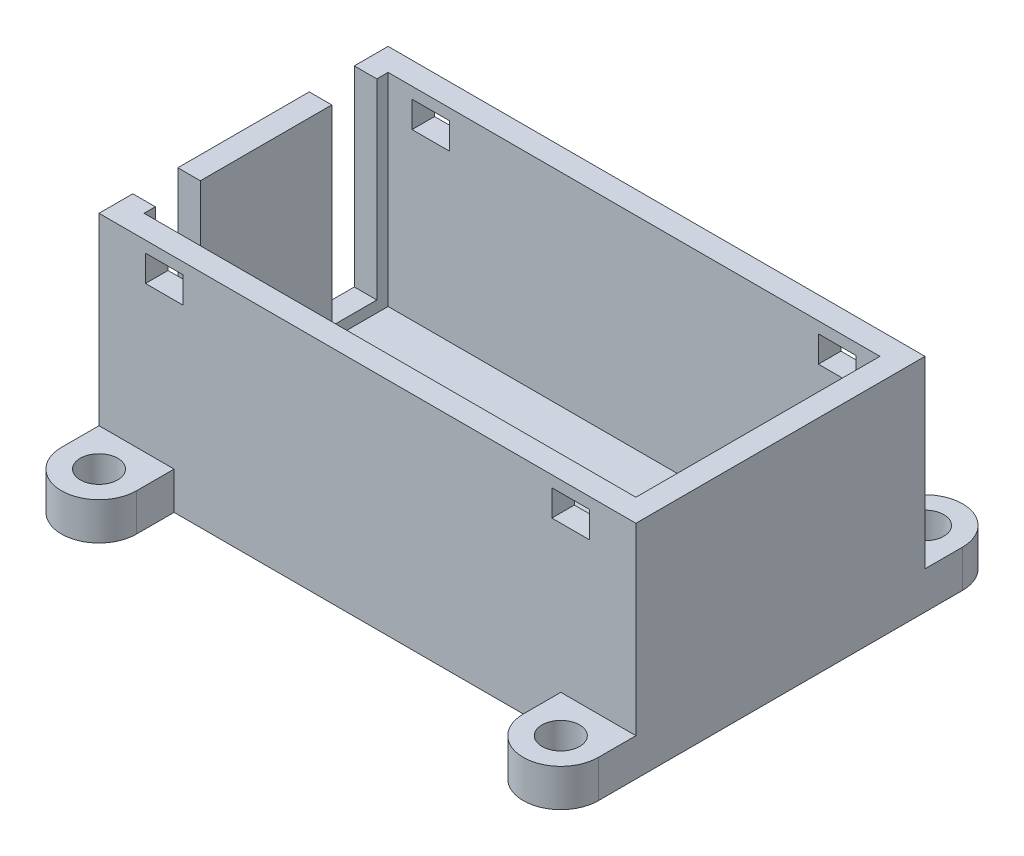
SolidWorks part; units mm, degrees
ref_plane "Front Plane" through (0, 0, 0) normal (0, 0, 1) x (1, 0, 0)
ref_plane "Top Plane" through (0, 0, 0) normal (0, 1, 0) x (1, 0, 0)
ref_plane "Right Plane" through (0, 0, 0) normal (1, 0, 0) x (0, 0, -1)
sketch "Sketch1" plane through (0, 0, 0) normal (0, 1, 0) x (1, 0, 0)
  line L0 (0, 0) -> (3, 0)
  line L1 (0, 0) -> (71.5, 0)
  line L2 (0, 0) -> (0, 38.5)
  line L3 (0, 38.5) -> (71.5, 38.5)
  line L4 (71.5, 0) -> (71.5, 38.5)
  line L5 (3, 0) -> (3, 3)
  line L7 (3, 3) -> (68.5, 3)
  line L8 (3, 3) -> (3, 35.5)
  line L9 (3, 35.5) -> (68.5, 35.5)
  line L10 (68.5, 3) -> (68.5, 35.5)
  dimension "D1" = 71.5
  dimension "D2" = 38.5
  dimension "D3" = 3
  dimension "D4" = 3
  dimension "D5" = 65.5
  dimension "D6" = 32.5
extrude "Boss-Extrude1" add sketch "Sketch1" against normal blind 29.5 contours L2 L3 L4 L1
extrude "Cut-Extrude1" cut sketch "Sketch1<4>" against normal blind 27 contours L8 L9 L10 L7
sketch "Sketch1<4>" plane through (0, 0, 0) normal (0, 1, 0) x (1, 0, 0) same geometry as "Sketch1"
sketch "Sketch3" plane through (0, 0, 0) normal (-1, 0, 0) x (0, 0, 1)
  line L0 (-4.5, -25.5) -> (-10.5, -25.5)
  line L2 (-19.25, 0) -> (-19.25, -9.1014)
  line L7 (-38.5, 0) -> (-34, 0)
  line L8 (0, -29.5) -> (-38.5, -29.5) construction
  line L13 (-34, -29.5) -> (-34, -25.5)
  line L14 (-34, 0) -> (-28, 0)
  line L15 (-34, 0) -> (-34, -25.5)
  line L16 (-34, -25.5) -> (-28, -25.5)
  line L17 (-28, 0) -> (-28, -25.5)
  line L18 (-10.5, 0) -> (-10.5, -25.5)
  line L19 (-4.5, 0) -> (-10.5, 0)
  line L20 (-4.5, 0) -> (-4.5, -25.5)
  dimension "D1" = 4.5
  dimension "D2" = 4
  dimension "D3" = 6
extrude "Cut-Extrude2" cut sketch "Sketch3" against normal blind 29 contours L20 L18 L0 | L15 L14 L17 L16 region at (0, -12.75, -7.5)
sketch "Sketch4" plane through (0, 0, -38.5) normal (0, 0, -1) x (-1, 0, 0)
  line L0 (-71.5, 0) -> (-65.3066, 0)
  line L1 (-3, 0) -> (-68.5, 0) construction
  line L2 (-65.3066, 0) -> (-65.3066, -5)
  line L3 (-71.5, 0) -> (0, 0)
  line L4 (-65.3066, -5) -> (-60.3066, -5)
  line L5 (-65.3066, -5) -> (-65.3066, -1.5)
  line L6 (-65.3066, -1.5) -> (-60.3066, -1.5)
  line L7 (-60.3066, -5) -> (-60.3066, -1.5)
  line L8 (-35.75, 0) -> (-35.75, -6.9018)
  line L9 (-11.1934, -5) -> (-11.1934, -1.5)
  line L10 (-6.1934, -1.5) -> (-11.1934, -1.5)
  line L11 (-6.1934, -5) -> (-6.1934, -1.5)
  line L12 (-6.1934, -5) -> (-11.1934, -5)
  dimension "D1" = 5
  dimension "D2" = 3.5
  dimension "D3" = 5
sketch "Sketch5" plane through (0, -29.5, 0) normal (0, -1, 0) x (1, 0, 0)
  line L0 (35.75, 0) -> (35.75, -38.5)
  line L1 (0, 0) -> (10, 0)
  line L2 (0, 0) -> (0, 5)
  line L4 (10, 0) -> (10, 5)
  line L6 (0, 0) -> (71.5, 0) construction
  line L8 (61.5, 0) -> (61.5, 5)
  line L9 (71.5, 0) -> (61.5, 0)
  line L10 (71.5, 0) -> (71.5, 5)
  line L19 (0, -38.5) -> (71.5, -38.5) construction
  line L20 (35.75, -19.25) -> (45.0495, -19.25)
  line L21 (71.5, -38.5) -> (71.5, -43.5)
  line L22 (71.5, -38.5) -> (61.5, -38.5)
  line L23 (61.5, -38.5) -> (61.5, -43.5)
  line L24 (10, -38.5) -> (10, -43.5)
  line L25 (0, -38.5) -> (0, -43.5)
  line L26 (0, -38.5) -> (10, -38.5)
  arc A0 (10, 5) -> (0, 5) centre (5, 5) ccw
  arc A1 (61.5, 5) -> (71.5, 5) centre (66.5, 5) cw
  circle A4 centre (5, 5) radius 2.5
  circle A5 centre (66.5, 5) radius 2.5
  circle A8 centre (66.5, -43.5) radius 2.5
  arc A9 (61.5, -43.5) -> (71.5, -43.5) centre (66.5, -43.5) ccw
  circle A10 centre (5, -43.5) radius 2.5
  arc A11 (10, -43.5) -> (0, -43.5) centre (5, -43.5) cw
  dimension "D3" = 5
  dimension "D1" = 5
  dimension "D2" = 10
  dimension "D4" = 5
extrude "Boss-Extrude3" add sketch "Sketch5" against normal blind 5 contours L9 L8 A1 L10
extrude "Boss-Extrude4" add sketch "Sketch5<5>" against normal blind 5 contours L4 A0 L2 L1
sketch "Sketch5<5>" plane through (0, -29.5, 0) normal (0, -1, 0) x (1, 0, 0) same geometry as "Sketch5"
extrude "Boss-Extrude5" add sketch "Sketch5<7>" against normal blind 5 contours L21 A9 L23 L22
sketch "Sketch5<7>" plane through (0, -29.5, 0) normal (0, -1, 0) x (1, 0, 0) same geometry as "Sketch5"
extrude "Boss-Extrude6" add sketch "Sketch5<8>" against normal blind 5 contours L24 A11 L25 L26
sketch "Sketch5<8>" plane through (0, -29.5, 0) normal (0, -1, 0) x (1, 0, 0) same geometry as "Sketch5"
extrude "Cut-Extrude3" cut sketch "Sketch5<9>" against normal blind 15 contours A5
sketch "Sketch5<9>" plane through (0, -29.5, 0) normal (0, -1, 0) x (1, 0, 0) same geometry as "Sketch5"
extrude "Cut-Extrude4" cut sketch "Sketch5<10>" against normal blind 20 contours A4
sketch "Sketch5<10>" plane through (0, -29.5, 0) normal (0, -1, 0) x (1, 0, 0) same geometry as "Sketch5"
extrude "Cut-Extrude5" cut sketch "Sketch5<11>" against normal blind 20 contours A10
sketch "Sketch5<11>" plane through (0, -29.5, 0) normal (0, -1, 0) x (1, 0, 0) same geometry as "Sketch5"
extrude "Cut-Extrude6" cut sketch "Sketch5<12>" against normal blind 20 contours A8
sketch "Sketch5<12>" plane through (0, -29.5, 0) normal (0, -1, 0) x (1, 0, 0) same geometry as "Sketch5"
extrude "Cut-Extrude7" cut sketch "Sketch4" against normal blind 63 contours L4 L7 L6 L5
extrude "Cut-Extrude8" cut sketch "Sketch4<3>" against normal blind 63 contours L9 L10 L11 L12
sketch "Sketch4<3>" plane through (0, 0, -38.5) normal (0, 0, -1) x (-1, 0, 0) same geometry as "Sketch4"
